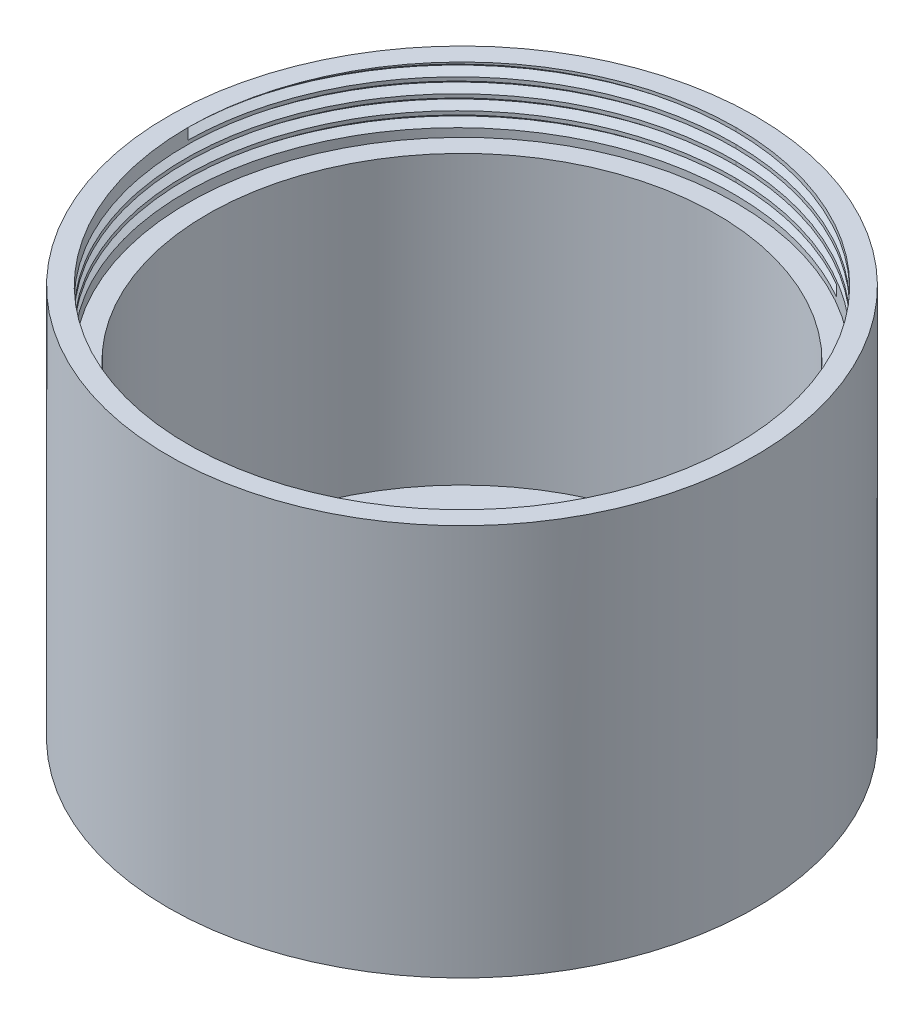
SolidWorks part; units mm, degrees
ref_plane "Front Plane" through (0, 0, 0) normal (0, 0, 1) x (1, 0, 0)
ref_plane "Top Plane" through (0, 0, 0) normal (0, 1, 0) x (1, 0, 0)
ref_plane "Right Plane" through (0, 0, 0) normal (1, 0, 0) x (0, 0, -1)
sketch "Sketch1" plane through (0, 0, 0) normal (0, 1, 0) x (1, 0, 0)
  circle A0 centre (0, 0) radius 90
  dimension "D1" = 180
extrude "Boss-Extrude1" add sketch "Sketch1" along normal blind 100
shell "Shell1" thickness 12 removed face at (0, 100, 90)
sketch "Sketch2" plane through (0, 0, 0) normal (0, 0, 1) x (1, 0, 0)
  line L0 (0, 0) -> (0, 220.2945) construction
  line L1 (-90, 100) -> (-84, 100)
  line L2 (-90, 100) -> (-90, 120)
  line L3 (-90, 120) -> (-84, 120)
  line L4 (-84, 100) -> (-84, 120)
  dimension "D1" = 20
  dimension "D2" = 6
revolve "Revolve1" add sketch "Sketch2" angle 360 about L0
thread "Thread1" pitch 4.5 method cut profile "Thread Profile1" start angle 0, offset 0, length 15, pitch 4.5, diameter 168
ref_plane "Plane1" through (-84, 120, 0) normal (0, 0, 1) x (-1, 0, 0)
sketch "Thread Profile1" plane through (-84, 120, 0) normal (0, 0, 1) x (-1, 0, 0)
  line L0 (0, 0) -> (0, 4.5) construction
  line L1 (0, 0) -> (2.4357, 1.4062)
  line L2 (2.4357, 1.4062) -> (2.4357, 1.9687)
  line L3 (2.4357, 1.9687) -> (0, 3.375)
  line L4 (2.4357, 1.6875) -> (0, 1.6875) construction
  line L11 (0, 0) -> (0, 3.375)
  point P2 (0, 0)
  dimension "Pitch" = 4.5
  dimension "Profile_Angle" = 60
  dimension "Profile_Land" = 0.5625
  dimension "Profile_Height" = 2.4357
